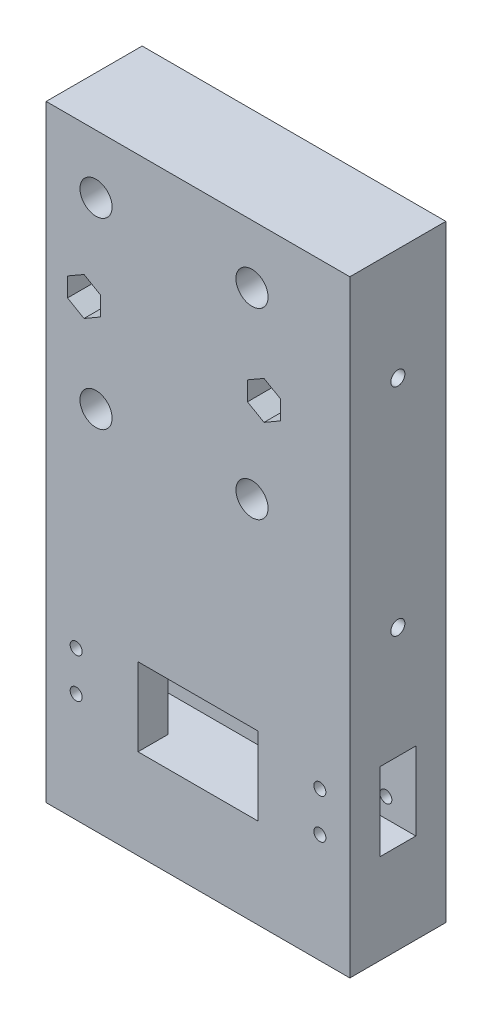
SolidWorks part; units mm, degrees
other "Markup1"
sketch "Sketch8" plane through (21.3115, 25, 0) normal (0.306, 0.1864, -0.9336) x (-0.9512, 0.0181, -0.3081)
ref_plane "Front Plane" through (0, 0, 0) normal (0, 0, 1) x (1, 0, 0)
ref_plane "Top Plane" through (0, 0, 0) normal (0, 1, 0) x (1, 0, 0)
ref_plane "Right Plane" through (0, 0, 0) normal (1, 0, 0) x (0, 0, -1)
sketch "Sketch1" plane through (0, 0, 0) normal (0, 0, 1) x (1, 0, 0)
  line L0 (0, 25) -> (0, -25) construction
  line L1 (21.3115, 25) -> (-21.3115, 25)
  line L2 (21.3115, 25) -> (21.3115, -25)
  line L3 (21.3115, -25) -> (-21.3115, -25)
  line L4 (-21.3115, 25) -> (-21.3115, -25)
  line L5 (21.3115, 25) -> (-21.3115, -25) construction
  line L6 (21.3115, -25) -> (-21.3115, 25) construction
  line L7 (-21.3115, 0) -> (21.3115, 0) construction
  circle A0 centre (-13, -15.25) radius 2.677
  circle A1 centre (13, -15.25) radius 2.677
  circle A2 centre (13, 15.25) radius 2.677
  circle A3 centre (-13, 15.25) radius 2.677
  point P0 (0, 0)
  dimension "D1" = 30.5
  dimension "D2" = 26
  dimension "D3" = 50
extrude "Boss-Extrude1" add sketch "Sketch1" along normal blind 16
sketch "Sketch2" plane through (0, 0, 0) normal (0, 0, 1) x (1, 0, 0)
  circle A0 centre (0, 0) radius 11
  dimension "D1" = 22
extrude "Cut-Extrude2" cut sketch "Sketch2" along normal blind 11
sketch "Sketch3" plane through (0, 0, 0) normal (0, 0, -1) x (-1, 0, 0)
  line L0 (0, 0) -> (-18.0234, 0) construction
  line L1 (0, 0) -> (0, 5.0894) construction
  circle A0 centre (-15, 0) radius 1.75
  circle A1 centre (15, 0) radius 1.75
  dimension "D1" = 15
  dimension "D2" = 3.5
extrude "Cut-Extrude3" cut sketch "Sketch3" against normal blind 10
sketch "Sketch9" plane through (0, 0, 0) normal (0, 0, -1) x (-1, 0, 0)
  line L0 (0, -11) -> (0, 11) construction
  line L1 (-15, 3.1754) -> (-17.75, 1.5877)
  line L2 (-17.75, 1.5877) -> (-17.75, -1.5877)
  line L3 (-17.75, -1.5877) -> (-15, -3.1754)
  line L4 (-15, -3.1754) -> (-12.25, -1.5877)
  line L5 (-12.25, -1.5877) -> (-12.25, 1.5877)
  line L6 (-12.25, 1.5877) -> (-15, 3.1754)
  line L7 (12.25, 1.5877) -> (15, 3.1754)
  line L8 (12.25, -1.5877) -> (12.25, 1.5877)
  line L9 (15, -3.1754) -> (12.25, -1.5877)
  line L10 (17.75, -1.5877) -> (15, -3.1754)
  line L11 (17.75, 1.5877) -> (17.75, -1.5877)
  line L12 (15, 3.1754) -> (17.75, 1.5877)
  circle A0 centre (-15, 0) radius 2.75 construction
  circle A1 centre (0, 0) radius 11 construction
  point P1 (-17.75, 0)
  dimension "D1" = 5.5
extrude "Cut-Extrude6" cut sketch "Sketch9" against normal through all from offset 5 offset against normal yes
sketch "Sketch30" plane through (0, -25, 0) normal (0, -1, 0) x (1, 0, 0)
  line L1 (-21.3115, 16) -> (21.3115, 16)
  line L2 (-21.3115, 16) -> (-21.3115, 0)
  line L3 (-21.3115, 0) -> (21.3115, 0)
  line L4 (21.3115, 16) -> (21.3115, 0)
extrude "Boss-Extrude8" add sketch "Sketch30" along normal blind 20.23
sketch "Sketch10" plane through (0, 0, 0) normal (0, 0, 1) x (1, 0, 0)
  line L0 (21.3115, -45.23) -> (-21.3115, -45.23)
  line L2 (-21.3115, -45.23) -> (-21.3115, -61.23)
  line L3 (-21.3115, -61.23) -> (21.3115, -61.23)
  line L4 (21.3115, -61.23) -> (21.3115, -45.23)
  dimension "D1" = 16
extrude "Boss-Extrude2" add sketch "Sketch10" along normal up to surface (16 mm away) up to face at (15, 0, 16)
sketch "Sketch14" plane through (-21.3115, 0, 0) normal (-1, 0, 0) x (0, 0, 1)
  line L0 (16, -61.23) -> (0, -61.23) construction
  line L1 (5, -61.23) -> (11, -61.23)
  line L2 (5, -61.23) -> (5, -48.23)
  line L3 (5, -48.23) -> (11, -48.23)
  line L4 (11, -61.23) -> (11, -48.23)
  line L7 (0, -61.23) -> (16, -61.23) construction
  point P6 (8, -61.23)
  point P7 (8, -61.23)
  dimension "D1" = 13
  dimension "D2" = 6
extrude "Cut-Extrude7" cut sketch "Sketch14" against normal through all
sketch "Sketch16" plane through (21.3115, 0, 0) normal (1, 0, 0) x (0, 0, -1)
  line L0 (-8, -48.23) -> (-8, 25)
  line L1 (-11, -48.23) -> (-5, -48.23) construction
  line L2 (-16, 25) -> (0, 25) construction
  line L4 (-16, 25) -> (0, 25)
  line L5 (-16, 25) -> (-16, -48.23)
  line L6 (-16, -48.23) -> (0, -48.23)
  line L7 (0, 25) -> (0, -48.23)
  line M6 (-11, -48.23) -> (-5, -48.23)
  line M9 (0, -61.23) -> (0, 25)
  line M10 (0, 25) -> (-16, 25)
  line M11 (-16, 25) -> (-16, -61.23)
extrude "Boss-Extrude3" add sketch "Sketch16" along normal blind 8 contours L6 L0 M11 M6 M10 | L6 L0 M6 M9 M10 region at (21.3115, -11.615, 12) region at (21.3115, -11.615, 4)
sketch "Sketch17" plane through (29.3115, 0, 0) normal (1, 0, 0) x (0, 0, -1)
  line L0 (-8, -48.23) -> (-8, 25)
  line L1 (-16, -48.23) -> (0, -48.23) construction
  line L2 (0, 25) -> (-16, 25) construction
  line L3 (-8, -11.615) -> (0, -11.615)
  line L4 (0, -48.23) -> (0, 25) construction
  circle A0 centre (-8, 6.385) radius 1.175
  circle A1 centre (-8, -29.615) radius 1.175
  point P8 (-8, -11.615)
  dimension "D2" = 2.35
  dimension "D1" = 18
extrude "Cut-Extrude9" cut sketch "Sketch17" against normal blind 8 contours L0 A0 | L0 A0 | A1 L0 | A1 L0 region at (29.3115, -29.615, 8.4987) region at (29.3115, 6.385, 8.4987) region at (29.3115, 6.385, 7.5013) region at (29.3115, -29.615, 7.5013)
sketch "Sketch18" plane through (0, 0, 0) normal (0, 0, -1) x (-1, 0, 0)
  line L0 (-25.3115, -48.23) -> (-25.3115, 25)
  line L1 (-29.3115, -48.23) -> (-21.3115, -48.23) construction
  line L2 (-29.3115, 25) -> (21.3115, 25) construction
  line L3 (-25.3115, -11.615) -> (-29.3115, -11.615)
  line L4 (-26.2115, 8.385) -> (-24.4115, 8.385)
  line L5 (-26.2115, 8.385) -> (-26.2115, 4.385)
  line L6 (-26.2115, 4.385) -> (-24.4115, 4.385)
  line L7 (-24.4115, 8.385) -> (-24.4115, 4.385)
  line L8 (-26.2115, 8.385) -> (-24.4115, 4.385) construction
  line L9 (-26.2115, 4.385) -> (-24.4115, 8.385) construction
  line L10 (-29.3115, -48.23) -> (-29.3115, 25) construction
  line L11 (-26.2115, -27.615) -> (-24.4115, -27.615)
  line L12 (-24.4115, -31.615) -> (-24.4115, -27.615)
  line L13 (-26.2115, -31.615) -> (-24.4115, -31.615)
  line L14 (-26.2115, -31.615) -> (-26.2115, -27.615)
  point P6 (-25.3115, 6.385)
  point P11 (-25.3115, -11.615)
  dimension "D1" = 18
  dimension "D2" = 4
  dimension "D3" = 1.8
extrude "Cut-Extrude10" cut sketch "Sketch18" against normal blind 10.2 contours L7 L4 L0 L6 | L5 L6 L0 L4 | L14 L11 L12 L13 region at (25.7615, 6.385, 0) region at (24.8615, 6.385, 0)
sketch "Sketch15" plane through (0, 0, 0) normal (0, 0, -1) x (-1, 0, 0)
  line L0 (21.3115, -61.23) -> (-21.3115, -61.23) construction
  line L1 (-29.3115, -23.2996) -> (21.3115, -23.2996)
  line L2 (-21.3115, -61.23) -> (-21.3115, -48.23)
  line L3 (-29.3115, -48.23) -> (-29.3115, 25) construction
  line L4 (-4, -23.2996) -> (-4, -61.23)
  line L7 (-21.3115, -61.23) -> (-21.3115, -48.23) construction
  line L8 (-21.3115, -48.23) -> (-21.3115, -61.23) construction
  line L9 (-21.3115, -54.73) -> (21.3115, -54.73)
  line L10 (21.3115, 25) -> (21.3115, -61.23) construction
  line L11 (21.3115, -54.73) -> (21.3115, -28)
  line L12 (21.3115, -28) -> (0, -28)
  line L13 (0, -28) -> (0, -61.23)
  circle A2 centre (16.3115, -58.03) radius 1
  circle A4 centre (16.3115, -51.43) radius 1
  point P11 (-21.3115, -61.23)
  dimension "D1" = 5
  dimension "D2" = 3.2
extrude "Cut-Extrude8" cut sketch "Sketch15" against normal through all and the other way through all contours A2 | A4
sketch "Sketch6" plane through (0, -48.23, 0) normal (0, -1, 0) x (1, 0, 0)
  line L0 (21.3115, 11) -> (-21.3115, 11) construction
  line L1 (4.517, 11) -> (-4.517, 11)
  line L2 (4.517, 11) -> (4.517, 13.3875)
  line L3 (4.517, 13.3875) -> (-4.517, 13.3875)
  line L4 (-4.517, 11) -> (-4.517, 13.3875)
  line L5 (4.517, 11) -> (-4.517, 13.3875) construction
  line L6 (4.517, 13.3875) -> (-4.517, 11) construction
  point P0 (0, 12.1938)
extrude "Cut-Extrude5" cut sketch "Sketch6" against normal blind 30 and the other way through all
sketch "Sketch20" plane through (0, -48.23, 0) normal (0, -1, 0) x (-1, 0, 0)
  line L1 (-21.3115, -16) -> (-29.3115, -16)
  line L2 (-21.3115, -16) -> (-21.3115, 0)
  line L3 (-21.3115, 0) -> (-29.3115, 0)
  line L4 (-29.3115, -16) -> (-29.3115, 0)
extrude "Boss-Extrude5" add sketch "Sketch20" along normal up to surface (13 mm away) up to face at (0, -61.23, 12.8469)
sketch "Sketch21" plane through (0, -61.23, 0) normal (0, -1, 0) x (-1, 0, 0)
  line L0 (-29.3115, -16) -> (-29.3115, 0) construction
  line L1 (-21.3115, -11) -> (-29.3115, -11)
  line L2 (-21.3115, -11) -> (-21.3115, -5)
  line L3 (-21.3115, -5) -> (-29.3115, -5)
  line L4 (-29.3115, -11) -> (-29.3115, -5)
extrude "Cut-Extrude11" cut sketch "Sketch21" against normal up to surface (13 mm away) up to face at (0, -48.23, 9)
sketch "Sketch22" plane through (0, 0, 0) normal (0, 0, -1) x (-1, 0, 0)
  line L0 (21.3115, -61.23) -> (-29.3115, -61.23) construction
  line L1 (-29.3115, -61.23) -> (-29.3115, 25) construction
  circle A0 centre (-24.3115, -58.03) radius 1
  circle A3 centre (-24.3115, -51.43) radius 1
  dimension "D1" = 2
  dimension "D2" = 3.2
  dimension "D3" = 5
  dimension "D4" = 6.6
  dimension "D5" = 2
  dimension "D6" = 5
extrude "Cut-Extrude12" cut sketch "Sketch22" against normal through all
sketch "Sketch24" plane through (0, -61.23, 0) normal (0, -1, 0) x (1, 0, 0)
  line L1 (-21.3115, 5) -> (29.3115, 5)
  line L2 (-21.3115, 5) -> (-21.3115, 0)
  line L3 (-21.3115, 0) -> (29.3115, 0)
  line L4 (29.3115, 5) -> (29.3115, 0)
extrude "Boss-Extrude6" add sketch "Sketch24" along normal blind 15
sketch "Sketch25" plane through (0, 0, 5) normal (0, 0, 1) x (1, 0, 0)
  line L0 (29.3115, -76.23) -> (-21.3115, -76.23) construction
  line L1 (-21.3115, -76.23) -> (29.3115, -76.23)
  line L2 (-21.3115, -76.23) -> (-21.3115, -61.23)
  line L3 (-21.3115, -61.23) -> (29.3115, -61.23)
  line L4 (29.3115, -76.23) -> (29.3115, -61.23)
extrude "Boss-Extrude7" add sketch "Sketch25" along normal up to surface (11 mm away) up to face at (23.3115, -58.03, 16)
sketch "Sketch26" plane through (0, -76.23, 0) normal (0, -1, 0) x (1, 0, 0)
  line L0 (4, 16) -> (4, 0)
  line L1 (29.3115, 16) -> (-21.3115, 16) construction
  line L2 (-21.3115, 0) -> (29.3115, 0) construction
  line L3 (4, 8) -> (-21.3115, 8)
  line L4 (-21.3115, 16) -> (-21.3115, 0) construction
  circle A0 centre (-14, 8) radius 1
  circle A1 centre (22, 8) radius 1
  dimension "D1" = 2
  dimension "D2" = 18
extrude "Cut-Extrude13" cut sketch "Sketch26" against normal blind 10 contours L3 A0 | L3 A0 | A1 region at (-14, -76.23, 7.5756) region at (-14, -76.23, 8.4244) region at (22, -76.23, 8)
sketch "Sketch27" plane through (0, 0, 0) normal (0, 0, -1) x (-1, 0, 0)
  line L0 (-24.4115, -31.615) -> (-24.4115, -27.615) construction
  line L1 (-24.0015, -71.33) -> (-20.0015, -71.33)
  line L2 (-24.0015, -71.33) -> (-24.0015, -73.13)
  line L3 (-24.0015, -73.13) -> (-20.0015, -73.13)
  line L4 (-20.0015, -71.33) -> (-20.0015, -73.13)
  line L5 (-24.0015, -71.33) -> (-20.0015, -73.13) construction
  line L6 (-24.0015, -73.13) -> (-20.0015, -71.33) construction
  line L8 (-26.2115, -31.615) -> (-24.4115, -31.615) construction
  line L12 (-29.3115, -76.23) -> (-29.3115, 25) construction
  line L13 (21.3115, -76.23) -> (-29.3115, -76.23) construction
  line L14 (-29.3115, -49.5626) -> (21.3115, -49.5626)
  line L15 (21.3115, 25) -> (21.3115, -76.23) construction
  line L16 (-4, -49.5626) -> (-4, -76.23)
  line L17 (16.0015, -73.13) -> (12.0015, -73.13)
  line L18 (12.0015, -71.33) -> (12.0015, -73.13)
  line L19 (16.0015, -71.33) -> (12.0015, -71.33)
  line L20 (16.0015, -71.33) -> (16.0015, -73.13)
  point P0 (-22.0015, -72.23)
  dimension "D1" = 7.31
  dimension "D2" = 3.1
extrude "Cut-Extrude14" cut sketch "Sketch27" against normal blind 10.2 contours L4 L1 L2 L3 | L20 L19 L18 L17 region at (22.0015, -72.23, 0) region at (-14.0015, -72.23, 0)
sketch "Sketch29" plane through (0, 0, 16) normal (0, 0, 1) x (1, 0, 0)
  line L0 (-16.3115, -51.43) -> (24.3115, -58.03)
  line L1 (24.3115, -51.43) -> (-16.3115, -58.03)
  line L2 (-16.3115, -51.43) -> (24.3115, -51.43)
  line L3 (-16.3115, -51.43) -> (-16.3115, -58.03)
  line L4 (-16.3115, -58.03) -> (24.3115, -58.03)
  line L5 (24.3115, -51.43) -> (24.3115, -58.03)
  line L7 (-6, -48.23) -> (14, -48.23)
  line L8 (-6, -48.23) -> (-6, -61.23)
  line L9 (-6, -61.23) -> (14, -61.23)
  line L10 (14, -48.23) -> (14, -61.23)
  line L11 (-6, -48.23) -> (14, -61.23) construction
  line L12 (-6, -61.23) -> (14, -48.23) construction
  circle A0 centre (-16.3115, -51.43) radius 1 construction
  point P4 (4, -54.73)
  dimension "D1" = 13
  dimension "D2" = 20
extrude "Cut-Extrude15" cut sketch "Sketch29" against normal up to surface (5 mm away) contours L10 L7 L8 L2 | L10 L2 L8 L0 L1 | L0 L8 L1 | L10 L4 L8 L9 | L10 L0 L1 L8 L4 | L10 L1 L0 region at (4, -52.718, 16) region at (-2.6667, -54.73, 16) region at (4, -49.83, 16) region at (10.6667, -54.73, 16) region at (4, -56.742, 16) region at (4, -59.63, 16) up to face at (-16.3115, -59.03, 11)
